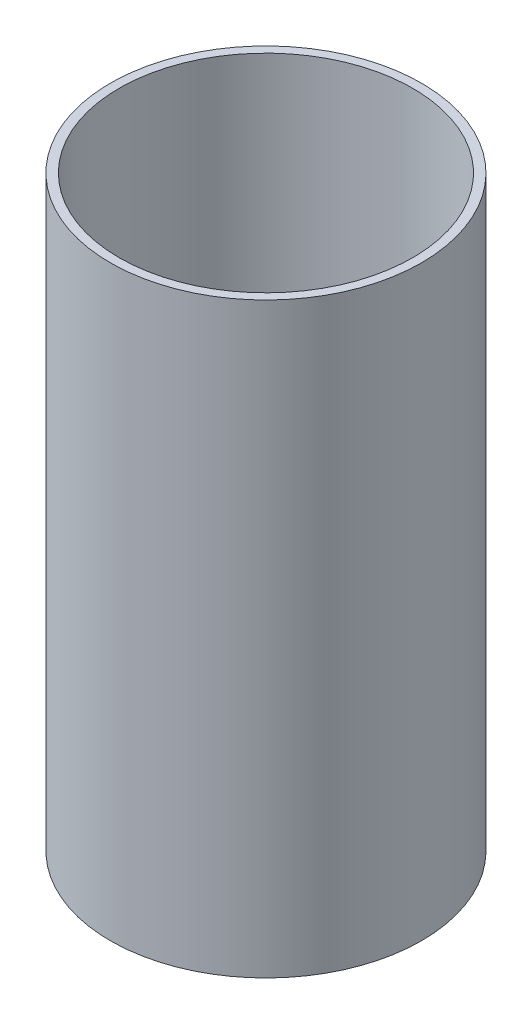
SolidWorks part; units mm, degrees
ref_plane "Ebene vorne" through (0, 0, 0) normal (0, 0, 1) x (1, 0, 0)
ref_plane "Ebene oben" through (0, 0, 0) normal (0, 1, 0) x (1, 0, 0)
ref_plane "Ebene rechts" through (0, 0, 0) normal (1, 0, 0) x (0, 0, -1)
sketch "Sketch1" plane through (0, 0, 0) normal (0, 1, 0) x (1, 0, 0)
  circle A0 centre (0, 0) radius 25
  dimension "D1" = 50
extrude "Extrude-Thin1" add sketch "Sketch1" along normal blind 100 thin thin type one direction wall 1.5
